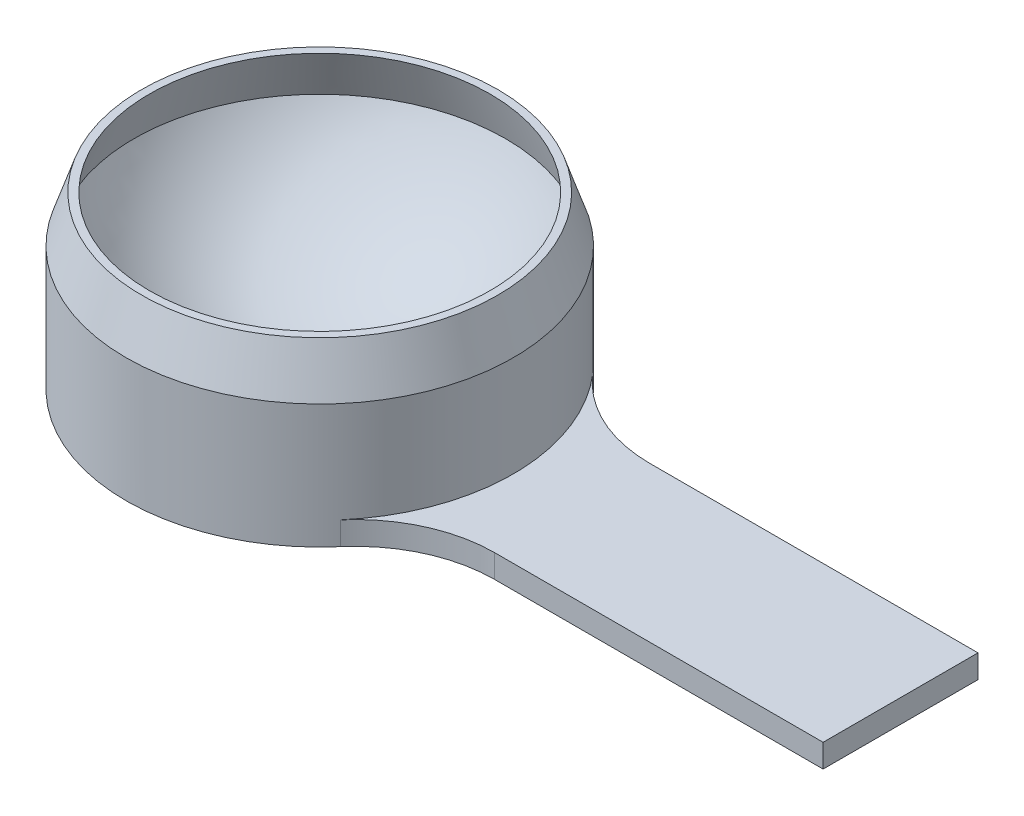
SolidWorks part; units mm, degrees
ref_plane "Front Plane" through (0, 0, 0) normal (0, 0, 1) x (1, 0, 0)
ref_plane "Top Plane" through (0, 0, 0) normal (0, 1, 0) x (1, 0, 0)
ref_plane "Right Plane" through (0, 0, 0) normal (1, 0, 0) x (0, 0, -1)
sketch "Sketch6" plane through (0, 0, 0) normal (1, 0, 0) x (0, 0, -1)
  line L0 (0, 0.6285) -> (0, 26.7591) construction
  line L1 (0, 0) -> (-25, 0)
  line L2 (-25, 0) -> (-25, 16)
  line L3 (-25, 16) -> (-23, 22)
  line L4 (-23, 22) -> (-22, 22)
  line L5 (-22, 22) -> (-24, 16)
  line L6 (-28.8389, 1) -> (21.196, 1) construction
  line L7 (0, 1) -> (0, 0)
  arc A0 (-24, 16) -> (0, 1) centre (0, 27.7) ccw
  point P15 (0, 2.0569)
  dimension "D1" = 50
  dimension "D2" = 46
  dimension "D3" = 16
  dimension "D4" = 22
  dimension "D5" = 1
  dimension "D6" = 1
  dimension "D7" = 1
  dimension "D8" = 1
revolve "Revolve1" add sketch "Sketch6" angle 360 about L0
sketch "Sketch7" plane through (0, 0, 0) normal (0, 1, 0) x (1, 0, 0)
  line L0 (0, 0) -> (76.175, 0) construction
  line L1 (25.353, 10) -> (60.2641, 10) construction
  line L2 (32.5505, 10.0003) -> (75, 10.0003)
  line L3 (75, 10.0003) -> (75, -10.0003)
  line L4 (32.5505, -10.0003) -> (75, -10.0003)
  arc A0 (18.9689, 16.2844) -> (32.5505, 10.0003) centre (32.6463, 28.0261) ccw
  circle A1 centre (0, 0) radius 25 construction
  arc A3 (18.9689, -16.2844) -> (32.5505, -10.0003) centre (32.6463, -28.0261) cw
  circle A4 centre (0, 0) radius 25
  arc A5 (18.9689, -16.2844) -> (18.9689, 16.2844) centre (0, 0) ccw
  point P14 (75, 0)
  dimension "D1" = 10
  dimension "D2" = 75
  dimension "D3" = 0
extrude "Boss-Extrude2" add sketch "Sketch7" along normal blind 3
